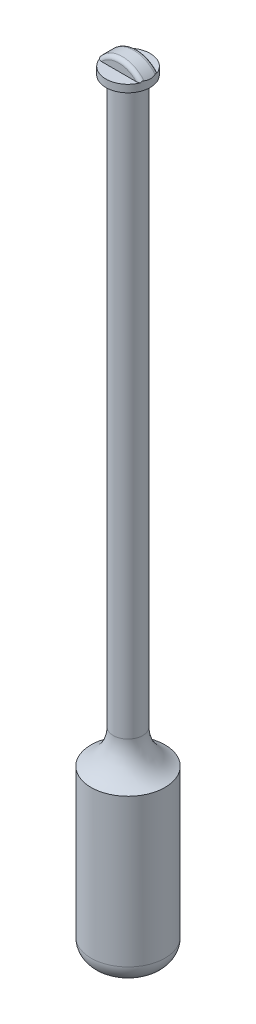
SolidWorks part; units mm, degrees
ref_plane "Front Plane" through (0, 0, 0) normal (0, 0, 1) x (1, 0, 0)
ref_plane "Top Plane" through (0, 0, 0) normal (0, 1, 0) x (1, 0, 0)
ref_plane "Right Plane" through (0, 0, 0) normal (1, 0, 0) x (0, 0, -1)
sketch "Sketch1" plane through (0, 0, 0) normal (0, 1, 0) x (1, 0, 0)
  circle A0 centre (0, 0) radius 10
  dimension "D1" = 20
extrude "Boss-Extrude1" add sketch "Sketch1" along normal blind 45
fillet "Fillet1" radius 5 1 edges at (0, 0, 10)
sketch "Sketch2" plane through (0, 45, 0) normal (0, 1, 0) x (1, 0, 0)
  circle A0 centre (0, 0) radius 4
  dimension "D1" = 8
extrude "Boss-Extrude2" add sketch "Sketch2" along normal blind 162
sketch "Sketch3" plane through (0, 207, 0) normal (0, 1, 0) x (1, 0, 0)
  circle A3 centre (0, 0) radius 6
  circle A4 centre (0, 0) radius 6
  dimension "D1" = 2
extrude "Boss-Extrude3" add sketch "Sketch3" along normal blind 2
sketch "Sketch4" plane through (0, 0, 0) normal (0, 0, 1) x (1, 0, 0)
  line L0 (0, 209) -> (0, 212) construction
  line L1 (6, 209) -> (-6, 209) construction
  line L2 (-6, 209) -> (6, 209)
  arc A0 (-6, 209) -> (6, 209) centre (0, 204.5) cw
  dimension "D1" = 3
extrude "Boss-Extrude4" add sketch "Sketch4" along normal mid plane 5
sketch "Sketch5" plane through (0, 207, 0) normal (0, -1, 0) x (1, 0, 0)
  circle A0 centre (0, 0) radius 6
extrude "Cut-Extrude2" cut sketch "Sketch5" against normal blind 5 flip side to cut
fillet "Fillet2" radius 10 1 edges at (0, 45, 4)
fillet "Fillet3" radius 1 2 edges at (0, 212, -2.5) (0, 212, 2.5)
